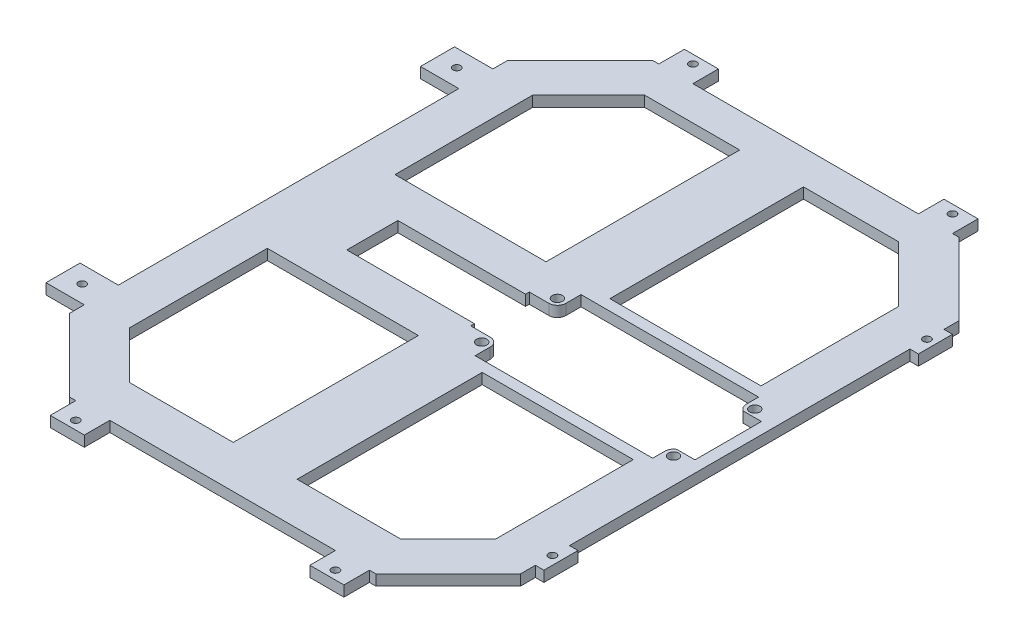
SolidWorks part; units mm, degrees
ref_plane "Front Plane" through (0, 0, 0) normal (0, 0, 1) x (1, 0, 0)
ref_plane "Top Plane" through (0, 0, 0) normal (0, 1, 0) x (1, 0, 0)
ref_plane "Right Plane" through (0, 0, 0) normal (1, 0, 0) x (0, 0, -1)
sketch "Sketch1" plane through (0, 0, 0) normal (0, 1, 0) x (1, 0, 0)
  line L1 (0, 0) -> (106, 0)
  line L2 (0, 0) -> (0, -137)
  line L3 (0, -137) -> (106, -137)
  line L4 (106, 0) -> (106, -137)
  line L5 (0, 0) -> (106, -137) construction
  line L6 (0, -137) -> (106, 0) construction
  point P4 (53, -68.5)
  dimension "D1" = 137
  dimension "D2" = 106
extrude "Boss-Extrude1" add sketch "Sketch1" along normal blind 2.5
sketch "Sketch2" plane through (0, 2.5, 0) normal (0, 1, 0) x (1, 0, 0)
  line L0 (0, -120) -> (17, -137)
  line L1 (0, 0) -> (0, -137) construction
  line L2 (0, -137) -> (106, -137) construction
  line L3 (17, -137) -> (0, -137)
  line L4 (0, -137) -> (0, -120)
  line L5 (89, -137) -> (106, -120)
  line L6 (106, -137) -> (106, 0) construction
  line L7 (106, -120) -> (106, -137)
  line L8 (106, -137) -> (89, -137)
  line L9 (89, 0) -> (106, -17)
  line L10 (106, 0) -> (0, 0) construction
  line L11 (106, -17) -> (106, 0)
  line L12 (106, 0) -> (89, 0)
  line L13 (0, 0) -> (17, 0)
  line L14 (17, 0) -> (0, -17)
  line L15 (0, -17) -> (0, 0)
  line L16 (10, -21.1421) -> (23.1421, -8)
  line L17 (23.1421, -8) -> (45.5, -8)
  line L18 (82.8579, -8) -> (96, -21.1421)
  line L19 (96, -21.1421) -> (96, -53.5)
  line L20 (96, -115.8579) -> (84.8579, -127)
  line L21 (84.8579, -127) -> (60.5, -127)
  line L22 (21.1421, -127) -> (10, -115.8579)
  line L23 (10, -115.8579) -> (10, -83.5)
  line L24 (96, -83.5) -> (96, -53.5) construction
  line L25 (10, -83.5) -> (45.5, -83.5)
  line L27 (10, -53.5) -> (45.5, -53.5)
  line L29 (0, -68.5) -> (106, -68.5) construction
  line L30 (45.5, -127) -> (21.1421, -127)
  line L31 (96, -83.5) -> (96, -115.8579)
  line L33 (10, -53.5) -> (10, -21.1421)
  line L34 (45.5, -127) -> (45.5, -83.5)
  line L36 (60.5, -127) -> (60.5, -83.5)
  line L37 (60.5, -53.5) -> (96, -53.5)
  line L38 (60.5, -8) -> (82.8579, -8)
  line L40 (45.5, -53.5) -> (45.5, -8)
  line L42 (60.5, -53.5) -> (60.5, -8)
  line L43 (60.5, -83.5) -> (96, -83.5)
  line L44 (53, -137) -> (53, 0) construction
  line L45 (45.5, -127) -> (60.5, -127) construction
  point P38 (96, -68.5)
  point P43 (53, -127)
  line M40 (0, 0) -> (0, -137)
  line M41 (0, -137) -> (106, -137)
  line M42 (106, -137) -> (106, 0)
  line M43 (106, 0) -> (0, 0)
  dimension "D1" = 17
  dimension "D2" = 17
  dimension "D3" = 17
  dimension "D4" = 17
  dimension "D5" = 17
  dimension "D6" = 17
  dimension "D7" = 17
  dimension "D8" = 17
  dimension "D9" = 8
  dimension "D10" = 10
  dimension "D11" = 10
  dimension "D12" = 10
  dimension "D13" = 10
  dimension "D14" = 10
  dimension "D15" = 10
  dimension "D16" = 10
  dimension "D17" = 30
  dimension "D18" = 15
  dimension "D19" = 15
extrude "Cut-Extrude1" cut sketch "Sketch2" against normal through all both and the other way through all contours L43 L36 L21 L20 L31 | L5 M41 M42 | L0 M40 M41 | L30 L34 L25 L23 L22 | L27 L40 L17 L16 L33 | L42 L37 L19 L18 L38 | L9 M43 M42 | L14 M43 M40 | L4 L0 L3 | L23 L25 L34 L30 L22 region at (5.6667, 2.5, 131.3333) region at (5.6667, 2.5, 5.6667) region at (100.3333, 2.5, 131.3333) region at (100.3333, 2.5, 5.6667) region at (28.5052, 2.5, 31.7876) region at (77.4948, 2.5, 31.7876) region at (77.6622, 2.5, 104.4947) region at (28.3378, 2.5, 104.4947)
sketch "Sketch3" plane through (0, 2.5, 0) normal (0, 1, 0) x (1, 0, 0)
  line L0 (54.2756, -77.39) -> (54.2756, -59.61) construction
  line L5 (100, -78.0568) -> (100, -58.9433) construction
  line L7 (106, -120) -> (106, -17) construction
  line L8 (106, -68.5) -> (0, -68.5) construction
  line L9 (0, -17) -> (0, -120) construction
  line L10 (56.2756, -80.94) -> (98, -80.94)
  line L15 (98, -80.94) -> (98, -78.0568)
  line L16 (100, -76.0568) -> (103.3, -76.0568)
  line L21 (103.3, -76.0568) -> (103.3, -60.9433)
  line L22 (103.3, -60.9433) -> (100, -60.9433)
  line L27 (98, -58.9433) -> (98, -56.06)
  line L28 (98, -56.06) -> (56.2756, -56.06)
  line L29 (56.2756, -56.06) -> (56.2756, -59.61)
  line L30 (56.2756, -77.39) -> (56.2756, -80.94)
  line L31 (54.2756, -75.39) -> (49.6756, -75.39)
  line L32 (49.6756, -75.39) -> (49.6756, -61.61)
  line L34 (54.2756, -61.61) -> (49.6756, -61.61)
  line L36 (103.3, -76.0568) -> (99.0318, -76.0568)
  line L37 (103.3, -76.0568) -> (103.3, -76.3068)
  line L38 (103.3, -76.3068) -> (99.0318, -76.3068)
  line L39 (99.0318, -76.0568) -> (99.0318, -76.3068)
  line L40 (103.3, -76.0568) -> (99.0318, -76.3068) construction
  line L41 (103.3, -76.3068) -> (99.0318, -76.0568) construction
  line L42 (103.3, -60.9433) -> (97.0368, -60.9433)
  line L43 (103.3, -60.9433) -> (103.3, -60.6933)
  line L44 (103.3, -60.6933) -> (97.0368, -60.6933)
  line L45 (97.0368, -60.9433) -> (97.0368, -60.6933)
  line L46 (103.3, -60.9433) -> (97.0368, -60.6933) construction
  line L47 (103.3, -60.6933) -> (97.0368, -60.9433) construction
  circle A0 centre (54.2756, -77.39) radius 2
  circle A1 centre (54.2756, -59.61) radius 2
  circle A2 centre (100, -78.0568) radius 2
  circle A3 centre (100, -58.9433) radius 2
  circle A4 centre (54.2756, -77.39) radius 1.2
  circle A5 centre (54.2756, -59.61) radius 1.2
  circle A6 centre (100, -58.9433) radius 1.2
  circle A7 centre (100, -78.0568) radius 1.2
  arc A8 (54.2756, -75.39) -> (56.2756, -77.39) centre (54.2756, -77.39) cw
  arc A9 (56.2756, -59.61) -> (52.2756, -59.61) centre (54.2756, -59.61) cw
  arc A10 (98, -58.9433) -> (100, -60.9433) centre (100, -58.9433) ccw
  arc A11 (98, -78.0568) -> (100, -76.0568) centre (100, -78.0568) cw
  point P10 (54.2756, -68.5)
  point P11 (100, -68.5)
  point P24 (77.2368, -68.8611)
  point P34 (100.0995, -68.5)
  point P47 (101.1659, -76.1818)
  point P50 (100.1684, -60.8183)
  dimension "D4" = 4
  dimension "D5" = 4
  dimension "D6" = 4
  dimension "D7" = 4
  dimension "D8" = 2.4
  dimension "D9" = 2.4
  dimension "D10" = 2.4
  dimension "D11" = 2.4
  dimension "D12" = 6
  dimension "D1" = 19.1135
  dimension "D2" = 17.78
  dimension "D3" = 45.7244
  dimension "D13" = 4.6
  dimension "D14" = 3.3
  dimension "D15" = 3.55
  dimension "D16" = 3.55
  dimension "D17" = 0.25
  dimension "D18" = 0.25
sketch "Sketch5" plane through (0, 0, 0) normal (0, 1, 0) x (1, 0, 0)
  line L0 (0, -68.5) -> (106, -68.5) construction
  line L1 (-4.5, -112.5) -> (110.5, -112.5) construction
  line L2 (-4.5, -112.5) -> (-4.5, -24.5) construction
  line L3 (-4.5, -24.5) -> (110.5, -24.5) construction
  line L4 (110.5, -112.5) -> (110.5, -24.5) construction
  line L5 (-4.5, -112.5) -> (110.5, -24.5) construction
  line L6 (-4.5, -24.5) -> (110.5, -112.5) construction
  line L7 (22.5, 4) -> (83.5, 4) construction
  line L8 (22.5, 4) -> (22.5, -141) construction
  line L9 (22.5, -141) -> (83.5, -141) construction
  line L10 (83.5, 4) -> (83.5, -141) construction
  line L11 (22.5, 4) -> (83.5, -141) construction
  line L12 (22.5, -141) -> (83.5, 4) construction
  line L13 (0, -17) -> (0, -120) construction
  line L14 (106, -120) -> (106, -17) construction
  line L15 (53, -137) -> (53, 0) construction
  line L16 (17, -137) -> (89, -137) construction
  line L17 (89, 0) -> (17, 0) construction
  line L23 (18.5, 0) -> (26.5, 0)
  line L24 (18.5, 0) -> (18.5, 6)
  line L29 (18.5, 6) -> (26.5, 6)
  line L30 (26.5, 0) -> (26.5, 6)
  line L35 (18.5, 0) -> (26.5, 6) construction
  line L36 (18.5, 6) -> (26.5, 0) construction
  line L41 (79.5, 6) -> (87.5, 6)
  line L42 (79.5, 6) -> (79.5, 0)
  line L43 (0, -116.5) -> (-9, -116.5)
  line L44 (0, -116.5) -> (0, -108.5)
  line L45 (0, -108.5) -> (-9, -108.5)
  line L46 (-9, -116.5) -> (-9, -108.5)
  line L47 (0, -116.5) -> (-9, -108.5) construction
  line L48 (0, -108.5) -> (-9, -116.5) construction
  line L49 (0, -28.5) -> (-9, -28.5)
  line L50 (0, -28.5) -> (0, -20.5)
  line L51 (0, -20.5) -> (-9, -20.5)
  line L52 (-9, -28.5) -> (-9, -20.5)
  line L53 (0, -28.5) -> (-9, -20.5) construction
  line L54 (0, -20.5) -> (-9, -28.5) construction
  line L59 (106, -116.5) -> (108, -116.5)
  line L60 (106, -116.5) -> (106, -108.5)
  line L65 (106, -108.5) -> (108, -108.5)
  line L66 (108, -116.5) -> (108, -108.5)
  line L67 (106, -116.5) -> (108, -108.5) construction
  line L68 (106, -108.5) -> (108, -116.5) construction
  line L69 (106, -28.5) -> (108, -28.5)
  line L70 (106, -28.5) -> (106, -20.5)
  line L71 (106, -20.5) -> (108, -20.5)
  line L72 (108, -28.5) -> (108, -20.5)
  line L73 (106, -28.5) -> (108, -20.5) construction
  line L74 (106, -20.5) -> (108, -28.5) construction
  line L75 (79.5, 0) -> (87.5, 0)
  line L76 (87.5, 6) -> (87.5, 0)
  line L77 (79.5, 6) -> (87.5, 0) construction
  line L78 (79.5, 0) -> (87.5, 6) construction
  line L79 (79.5, -137) -> (87.5, -137)
  line L80 (79.5, -137) -> (79.5, -143)
  line L81 (79.5, -143) -> (87.5, -143)
  line L82 (87.5, -137) -> (87.5, -143)
  line L83 (79.5, -137) -> (87.5, -143) construction
  line L84 (79.5, -143) -> (87.5, -137) construction
  line L85 (18.5, -137) -> (26.5, -137)
  line L86 (18.5, -137) -> (18.5, -143)
  line L87 (18.5, -143) -> (26.5, -143)
  line L88 (26.5, -137) -> (26.5, -143)
  line L89 (18.5, -137) -> (26.5, -143) construction
  line L90 (18.5, -143) -> (26.5, -137) construction
  circle A0 centre (-4.5, -112.5) radius 0.9
  circle A1 centre (-4.5, -24.5) radius 0.9
  circle A2 centre (22.5, 4) radius 0.9
  circle A3 centre (83.5, 4) radius 0.9
  circle A6 centre (83.5, -141) radius 0.9
  circle A7 centre (22.5, -141) radius 0.9
  circle A8 centre (106, -112.5) radius 0.9
  circle A9 centre (106, -24.5) radius 0.9
  point P4 (53, -68.5)
  point P9 (53, -68.5)
  point P27 (22.5, 3)
  point P28 (22.5, -141)
  point P29 (22.5, 6)
  point P32 (83.5, -141)
  point P35 (83.5, 3)
  point P36 (83.5, 6)
  point P37 (83.5, 4)
  point P42 (22.5, 4)
  point P48 (-4.5, -112.5)
  point P52 (-4.5, -24.5)
  point P57 (107, -112.5)
  point P62 (107, -24.5)
  point P70 (83.5, -140)
  point P73 (83.5, -143)
  point P78 (22.5, -140)
  point P79 (0, 0)
  dimension "D13" = 1.8
  dimension "D14" = 1.8
  dimension "D15" = 1.8
  dimension "D16" = 1.8
  dimension "D17" = 8
  dimension "D18" = 2
  dimension "D19" = 1.8
  dimension "D20" = 1.8
  dimension "D21" = 1.8
  dimension "D22" = 1.8
  dimension "D1" = 61
  dimension "D2" = 145
  dimension "D3" = 88
  dimension "D4" = 115
  dimension "D5" = 8
  dimension "D6" = 8
  dimension "D7" = 6
  dimension "D8" = 6
  dimension "D9" = 8
  dimension "D10" = 8
  dimension "D11" = 2
  dimension "D12" = 8
  dimension "D23" = 8
  dimension "D24" = 6
  dimension "D25" = 8
  dimension "D26" = 6
extrude "Boss-Extrude4" add sketch "Sketch5" along normal up to surface (2.5 mm away) contours A8 L60 L59 L66 L65 | A6 | L30 A7 | L46 L43 L44 L45 A0 | L52 L49 L50 L51 A1 | L79 L82 L81 L80 A2 | A3 | A9 L70 L69 L72 L71 region at (22.5, 0, -2.944) region at (83.5, 0, -2.944) region at (-4.5, 0, 116.3796) region at (-4.5, 0, 28.3796) region at (107.0534, 0, 112.5) region at (107.0534, 0, 24.5) region at (83.5, 0, 139.944) region at (22.5, 0, 139.944) up to face at (26.8284, 2.5, 28.8284)
ref_plane "Plane1" through (53, 0, 0) normal (-1, 0, 0) x (0, 0, 1)
ref_plane "Plane2" through (0, 0, 68.5) normal (0, 0, 1) x (1, 0, 0)
extrude "Cut-Extrude4" cut sketch "Sketch3" against normal through all both and the other way through all contours A3 L27 L28 L29 A1 L32 L31 A0 L30 L10 L15 A2 L16 L21 L22 | A5 | A4 | A7 | A6 | L43 L42 L45 L44 | L37 L36 L39 L38 region at (76.8671, 2.5, 68.5032) region at (54.2756, 2.5, 77.39) region at (54.2756, 2.5, 59.61) region at (100, 2.5, 58.9433) region at (100, 2.5, 78.0568)
sketch "Sketch7" plane through (0, 2.5, 0) normal (0, 1, 0) x (1, 0, 0)
  line L0 (49.6756, -75.39) -> (49.6756, -61.61) construction
  line L1 (49.6756, -62.5) -> (19.6756, -62.5)
  line L2 (49.6756, -62.5) -> (49.6756, -74.5)
  line L3 (49.6756, -74.5) -> (19.6756, -74.5)
  line L4 (19.6756, -62.5) -> (19.6756, -74.5)
  line L5 (49.6756, -62.5) -> (19.6756, -74.5) construction
  line L6 (49.6756, -74.5) -> (19.6756, -62.5) construction
  line L7 (49.6756, -68.5) -> (103.3, -68.5) construction
  line L8 (103.3, -76.3068) -> (103.3, -60.6933) construction
  point P4 (34.6756, -68.5)
  point P7 (49.6756, -68.5)
  dimension "D1" = 12
  dimension "D2" = 30
extrude "Cut-Extrude5" cut sketch "Sketch7" against normal through all both and the other way through all
sketch "Sketch8" plane through (0, 2.5, 0) normal (0, 1, 0) x (1, 0, 0)
  line L0 (106, -25.4) -> (106, -23.6) construction
  line L1 (106, -113.4) -> (106, -111.6) construction
  circle A0 centre (106, -24.5) radius 0.9
  circle A1 centre (106, -112.5) radius 0.9
extrude "Cut-Extrude6" cut sketch "Sketch8" against normal through all both and the other way through all
